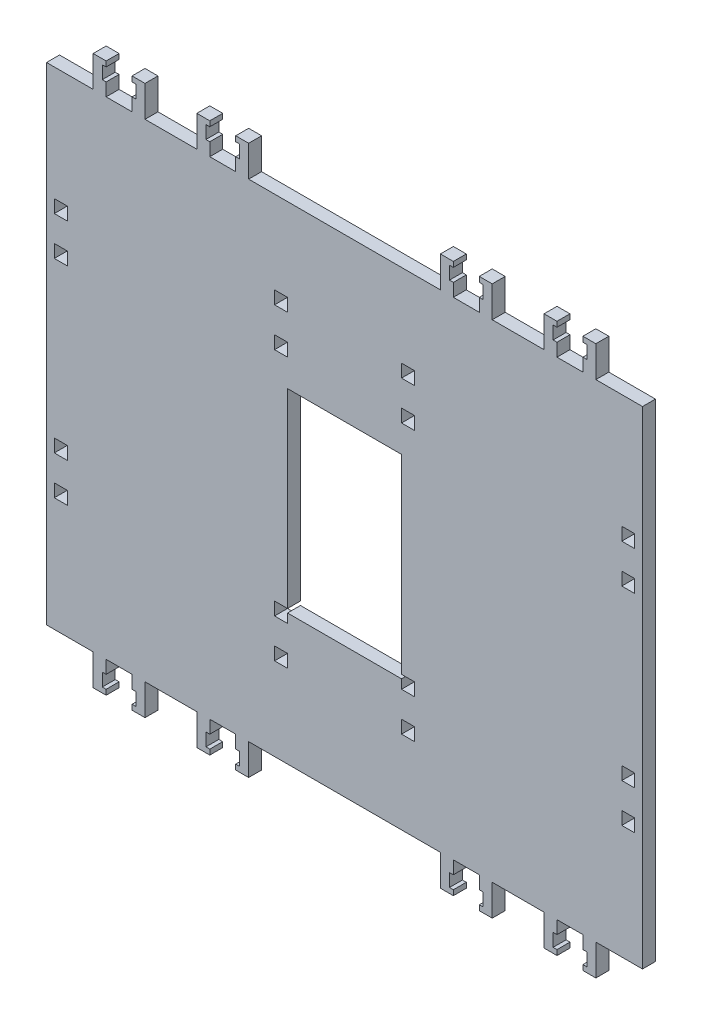
SolidWorks part; units mm, degrees
ref_plane "Plan de face" through (0, 0, 0) normal (0, 0, 1) x (1, 0, 0)
ref_plane "Plan de dessus" through (0, 0, 0) normal (0, 1, 0) x (1, 0, 0)
ref_plane "Plan de droite" through (0, 0, 0) normal (1, 0, 0) x (0, 0, -1)
sketch "Esquisse1" plane through (0, 0, 0) normal (0, 0, 1) x (1, 0, 0)
  line L0 (0, 0) -> (0, 94) construction
  line L1 (-21.3539, 94) -> (23.6911, 94) construction
  line L2 (-30, 188) -> (-45, 188)
  line L3 (-45, 188) -> (-45, 0) construction
  line L4 (-45, 0) -> (-30, 0)
  line L5 (-10, 0) -> (10, 0)
  line L6 (30, 0) -> (45, 0)
  line L7 (45, 0) -> (45, 188) construction
  line L8 (45, 188) -> (30, 188)
  line L9 (10, 188) -> (-10, 188)
  line L10 (-45, 188) -> (-45, 125.5) construction
  line L11 (-45, 125.5) -> (-89, 125.5)
  line L12 (-67, 125.5) -> (-67, 50.5) construction
  line L13 (-67, 50.5) -> (-45, 50.5)
  line L14 (-45, 50.5) -> (-45, 0) construction
  line L15 (-67, 50.5) -> (-89, 50.5)
  line L16 (-89, 50.5) -> (-89, 0) construction
  line L17 (-89, 0) -> (-104, 0)
  line L18 (-124, 0) -> (-144, 0)
  line L19 (-164, 0) -> (-179, 0)
  line L20 (-179, 0) -> (-179, 188) construction
  line L21 (-179, 188) -> (-164, 188)
  line L22 (-144, 188) -> (-124, 188)
  line L23 (-89, 188) -> (-89, 125.5) construction
  line L24 (-104, 188) -> (-89, 188)
  line L25 (-179, 0) -> (-179, 188) construction
  line L26 (-179, 0) -> (-174, 0) construction
  line L27 (-89, 125.5) -> (-89, 50.5)
  line L28 (-45, 50.5) -> (-45, 125.5)
  line L29 (-89, 188) -> (-45, 188)
  line L30 (-89, 0) -> (-45, 0)
  line L31 (45, 188) -> (48, 188)
  line L32 (48, 188) -> (48, 0)
  line L33 (48, 0) -> (45, 0)
  line L34 (-182, 0) -> (-179, 0)
  line L35 (-179, 188) -> (-182, 188)
  line L36 (-182, 188) -> (-182, 0)
  point P23 (-89, 33.0232)
  point P40 (0, 0)
  line B0 (20, 188) -> (20, 176.135) construction
  line B1 (20, 188) -> (15, 188)
  line B2 (15, 193) -> (10, 193) construction
  line B3 (10, 193) -> (10, 188)
  line B4 (15, 193) -> (15, 188)
  line B5 (20, 188) -> (25, 188)
  line B6 (25, 188) -> (25, 193)
  line B7 (25, 193) -> (30, 193) construction
  line B8 (30, 193) -> (30, 188)
  line B9 (10, 193) -> (10, 200)
  line B10 (10, 200) -> (15, 200)
  line B11 (15, 200) -> (15, 198)
  line B12 (15, 198) -> (13.5, 198)
  line B13 (13.5, 198) -> (13.5, 193)
  line B14 (13.5, 193) -> (15, 193)
  line B15 (25, 198) -> (26.5, 198)
  line B16 (30, 200) -> (25, 200)
  line B17 (25, 200) -> (25, 198)
  line B18 (26.5, 198) -> (26.5, 193)
  line B19 (30, 193) -> (30, 200)
  line B20 (30, 193) -> (30, 188)
  line B21 (25, 193) -> (26.5, 193)
  line B22 (-20, 188) -> (-20, 176.135) construction
  line B23 (-20, 188) -> (-25, 188)
  line B24 (-25, 193) -> (-30, 193) construction
  line B25 (-30, 193) -> (-30, 188)
  line B26 (-25, 193) -> (-25, 188)
  line B27 (-20, 188) -> (-15, 188)
  line B28 (-15, 188) -> (-15, 193)
  line B29 (-15, 193) -> (-10, 193) construction
  line B30 (-10, 193) -> (-10, 188)
  line B31 (-30, 193) -> (-30, 200)
  line B32 (-30, 200) -> (-25, 200)
  line B33 (-25, 200) -> (-25, 198)
  line B34 (-25, 198) -> (-26.5, 198)
  line B35 (-26.5, 198) -> (-26.5, 193)
  line B36 (-26.5, 193) -> (-25, 193)
  line B37 (-15, 198) -> (-13.5, 198)
  line B38 (-10, 200) -> (-15, 200)
  line B39 (-15, 200) -> (-15, 198)
  line B40 (-13.5, 198) -> (-13.5, 193)
  line B41 (-10, 193) -> (-10, 200)
  line B42 (-10, 193) -> (-10, 188)
  line B43 (-15, 193) -> (-13.5, 193)
  line B44 (20, 0) -> (20, 11.865) construction
  line B45 (20, 0) -> (15, 0)
  line B46 (15, -5) -> (10, -5) construction
  line B47 (10, -5) -> (10, 0)
  line B48 (15, -5) -> (15, 0)
  line B49 (20, 0) -> (25, 0)
  line B50 (25, 0) -> (25, -5)
  line B51 (25, -5) -> (30, -5) construction
  line B52 (30, -5) -> (30, 0)
  line B53 (10, -5) -> (10, -12)
  line B54 (10, -12) -> (15, -12)
  line B55 (15, -12) -> (15, -10)
  line B56 (15, -10) -> (13.5, -10)
  line B57 (13.5, -10) -> (13.5, -5)
  line B58 (13.5, -5) -> (15, -5)
  line B59 (25, -10) -> (26.5, -10)
  line B60 (30, -12) -> (25, -12)
  line B61 (25, -12) -> (25, -10)
  line B62 (26.5, -10) -> (26.5, -5)
  line B63 (30, -5) -> (30, -12)
  line B64 (30, -5) -> (30, 0)
  line B65 (25, -5) -> (26.5, -5)
  line B66 (-20, 0) -> (-20, 11.865) construction
  line B67 (-20, 0) -> (-25, 0)
  line B68 (-25, -5) -> (-30, -5) construction
  line B69 (-30, -5) -> (-30, 0)
  line B70 (-25, -5) -> (-25, 0)
  line B71 (-20, 0) -> (-15, 0)
  line B72 (-15, 0) -> (-15, -5)
  line B73 (-15, -5) -> (-10, -5) construction
  line B74 (-10, -5) -> (-10, 0)
  line B75 (-30, -5) -> (-30, -12)
  line B76 (-30, -12) -> (-25, -12)
  line B77 (-25, -12) -> (-25, -10)
  line B78 (-25, -10) -> (-26.5, -10)
  line B79 (-26.5, -10) -> (-26.5, -5)
  line B80 (-26.5, -5) -> (-25, -5)
  line B81 (-15, -10) -> (-13.5, -10)
  line B82 (-10, -12) -> (-15, -12)
  line B83 (-15, -12) -> (-15, -10)
  line B84 (-13.5, -10) -> (-13.5, -5)
  line B85 (-10, -5) -> (-10, -12)
  line B86 (-10, -5) -> (-10, 0)
  line B87 (-15, -5) -> (-13.5, -5)
  line B88 (-154, 188) -> (-154, 176.135) construction
  line B89 (-154, 188) -> (-149, 188)
  line B90 (-149, 193) -> (-144, 193) construction
  line B91 (-144, 193) -> (-144, 188)
  line B92 (-149, 193) -> (-149, 188)
  line B93 (-154, 188) -> (-159, 188)
  line B94 (-159, 188) -> (-159, 193)
  line B95 (-159, 193) -> (-164, 193) construction
  line B96 (-164, 193) -> (-164, 188)
  line B97 (-144, 193) -> (-144, 200)
  line B98 (-144, 200) -> (-149, 200)
  line B99 (-149, 200) -> (-149, 198)
  line B100 (-149, 198) -> (-147.5, 198)
  line B101 (-147.5, 198) -> (-147.5, 193)
  line B102 (-147.5, 193) -> (-149, 193)
  line B103 (-159, 198) -> (-160.5, 198)
  line B104 (-164, 200) -> (-159, 200)
  line B105 (-159, 200) -> (-159, 198)
  line B106 (-160.5, 198) -> (-160.5, 193)
  line B107 (-164, 193) -> (-164, 200)
  line B108 (-164, 193) -> (-164, 188)
  line B109 (-159, 193) -> (-160.5, 193)
  line B110 (-114, 0) -> (-114, 11.865) construction
  line B111 (-114, 0) -> (-109, 0)
  line B112 (-109, -5) -> (-104, -5) construction
  line B113 (-104, -5) -> (-104, 0)
  line B114 (-109, -5) -> (-109, 0)
  line B115 (-114, 0) -> (-119, 0)
  line B116 (-119, 0) -> (-119, -5)
  line B117 (-119, -5) -> (-124, -5) construction
  line B118 (-124, -5) -> (-124, 0)
  line B119 (-104, -5) -> (-104, -12)
  line B120 (-104, -12) -> (-109, -12)
  line B121 (-109, -12) -> (-109, -10)
  line B122 (-109, -10) -> (-107.5, -10)
  line B123 (-107.5, -10) -> (-107.5, -5)
  line B124 (-107.5, -5) -> (-109, -5)
  line B125 (-119, -10) -> (-120.5, -10)
  line B126 (-124, -12) -> (-119, -12)
  line B127 (-119, -12) -> (-119, -10)
  line B128 (-120.5, -10) -> (-120.5, -5)
  line B129 (-124, -5) -> (-124, -12)
  line B130 (-124, -5) -> (-124, 0)
  line B131 (-119, -5) -> (-120.5, -5)
  line B132 (-154, 0) -> (-154, 11.865) construction
  line B133 (-154, 0) -> (-149, 0)
  line B134 (-149, -5) -> (-144, -5) construction
  line B135 (-144, -5) -> (-144, 0)
  line B136 (-149, -5) -> (-149, 0)
  line B137 (-154, 0) -> (-159, 0)
  line B138 (-159, 0) -> (-159, -5)
  line B139 (-159, -5) -> (-164, -5) construction
  line B140 (-164, -5) -> (-164, 0)
  line B141 (-144, -5) -> (-144, -12)
  line B142 (-144, -12) -> (-149, -12)
  line B143 (-149, -12) -> (-149, -10)
  line B144 (-149, -10) -> (-147.5, -10)
  line B145 (-147.5, -10) -> (-147.5, -5)
  line B146 (-147.5, -5) -> (-149, -5)
  line B147 (-159, -10) -> (-160.5, -10)
  line B148 (-164, -12) -> (-159, -12)
  line B149 (-159, -12) -> (-159, -10)
  line B150 (-160.5, -10) -> (-160.5, -5)
  line B151 (-164, -5) -> (-164, -12)
  line B152 (-164, -5) -> (-164, 0)
  line B153 (-159, -5) -> (-160.5, -5)
  line B154 (-114, 188) -> (-114, 176.135) construction
  line B155 (-114, 188) -> (-109, 188)
  line B156 (-109, 193) -> (-104, 193) construction
  line B157 (-104, 193) -> (-104, 188)
  line B158 (-109, 193) -> (-109, 188)
  line B159 (-114, 188) -> (-119, 188)
  line B160 (-119, 188) -> (-119, 193)
  line B161 (-119, 193) -> (-124, 193) construction
  line B162 (-124, 193) -> (-124, 188)
  line B163 (-104, 193) -> (-104, 200)
  line B164 (-104, 200) -> (-109, 200)
  line B165 (-109, 200) -> (-109, 198)
  line B166 (-109, 198) -> (-107.5, 198)
  line B167 (-107.5, 198) -> (-107.5, 193)
  line B168 (-107.5, 193) -> (-109, 193)
  line B169 (-119, 198) -> (-120.5, 198)
  line B170 (-124, 200) -> (-119, 200)
  line B171 (-119, 200) -> (-119, 198)
  line B172 (-120.5, 198) -> (-120.5, 193)
  line B173 (-124, 193) -> (-124, 200)
  line B174 (-124, 193) -> (-124, 188)
  line B175 (-119, 193) -> (-120.5, 193)
  line B176 (42.5, 129) -> (42.5, 139) construction
  line B177 (40, 129) -> (40, 124)
  line B178 (40, 129) -> (45, 129)
  line B179 (45, 129) -> (45, 124)
  line B180 (40, 124) -> (45, 124)
  line B181 (40, 139) -> (40, 144)
  line B182 (40, 139) -> (45, 139)
  line B183 (45, 139) -> (45, 144)
  line B184 (40, 144) -> (45, 144)
  line B185 (42.5, 134) -> (35.5276, 134) construction
  circle B186 centre (42.5, 134) radius 2 construction
  line B187 (42.5, 59) -> (42.5, 49) construction
  line B188 (40, 59) -> (40, 64)
  line B189 (40, 59) -> (45, 59)
  line B190 (45, 59) -> (45, 64)
  line B191 (40, 64) -> (45, 64)
  line B192 (40, 49) -> (40, 44)
  line B193 (40, 49) -> (45, 49)
  line B194 (45, 49) -> (45, 44)
  line B195 (40, 44) -> (45, 44)
  line B196 (42.5, 54) -> (35.5276, 54) construction
  circle B197 centre (42.5, 54) radius 2 construction
  line B198 (-176.5, 129) -> (-176.5, 139) construction
  line B199 (-174, 129) -> (-174, 124)
  line B200 (-174, 129) -> (-179, 129)
  line B201 (-179, 129) -> (-179, 124)
  line B202 (-174, 124) -> (-179, 124)
  line B203 (-174, 139) -> (-174, 144)
  line B204 (-174, 139) -> (-179, 139)
  line B205 (-179, 139) -> (-179, 144)
  line B206 (-174, 144) -> (-179, 144)
  line B207 (-176.5, 134) -> (-169.5276, 134) construction
  circle B208 centre (-176.5, 134) radius 2 construction
  line B209 (-176.5, 59) -> (-176.5, 49) construction
  line B210 (-174, 59) -> (-174, 64)
  line B211 (-174, 59) -> (-179, 59)
  line B212 (-179, 59) -> (-179, 64)
  line B213 (-174, 64) -> (-179, 64)
  line B214 (-174, 49) -> (-174, 44)
  line B215 (-174, 49) -> (-179, 49)
  line B216 (-179, 49) -> (-179, 44)
  line B217 (-174, 44) -> (-179, 44)
  line B218 (-176.5, 54) -> (-169.5276, 54) construction
  circle B219 centre (-176.5, 54) radius 2 construction
  line B220 (-91.5, 141) -> (-91.5, 151) construction
  line B221 (-89, 141) -> (-89, 136)
  line B222 (-89, 141) -> (-94, 141)
  line B223 (-94, 141) -> (-94, 136)
  line B224 (-89, 136) -> (-94, 136)
  line B225 (-89, 151) -> (-89, 156)
  line B226 (-89, 151) -> (-94, 151)
  line B227 (-94, 151) -> (-94, 156)
  line B228 (-89, 156) -> (-94, 156)
  line B229 (-91.5, 146) -> (-84.5276, 146) construction
  circle B230 centre (-91.5, 146) radius 2 construction
  line B231 (-42.5, 141) -> (-42.5, 151) construction
  line B232 (-45, 141) -> (-45, 136)
  line B233 (-45, 141) -> (-40, 141)
  line B234 (-40, 141) -> (-40, 136)
  line B235 (-45, 136) -> (-40, 136)
  line B236 (-45, 151) -> (-45, 156)
  line B237 (-45, 151) -> (-40, 151)
  line B238 (-40, 151) -> (-40, 156)
  line B239 (-45, 156) -> (-40, 156)
  line B240 (-42.5, 146) -> (-49.4724, 146) construction
  circle B241 centre (-42.5, 146) radius 2 construction
  line B242 (-91.5, 37) -> (-91.5, 47) construction
  line B243 (-89, 37) -> (-89, 32)
  line B244 (-89, 37) -> (-94, 37)
  line B245 (-94, 37) -> (-94, 32)
  line B246 (-89, 32) -> (-94, 32)
  line B247 (-89, 47) -> (-89, 52)
  line B248 (-89, 47) -> (-94, 47)
  line B249 (-94, 47) -> (-94, 52)
  line B250 (-89, 52) -> (-94, 52)
  line B251 (-91.5, 42) -> (-84.5276, 42) construction
  circle B252 centre (-91.5, 42) radius 2 construction
  line B253 (-42.5, 37) -> (-42.5, 47) construction
  line B254 (-45, 37) -> (-45, 32)
  line B255 (-45, 37) -> (-40, 37)
  line B256 (-40, 37) -> (-40, 32)
  line B257 (-45, 32) -> (-40, 32)
  line B258 (-45, 47) -> (-45, 52)
  line B259 (-45, 47) -> (-40, 47)
  line B260 (-40, 47) -> (-40, 52)
  line B261 (-45, 52) -> (-40, 52)
  line B262 (-42.5, 42) -> (-49.4724, 42) construction
  circle B263 centre (-42.5, 42) radius 2 construction
  dimension "D2" = 15
  dimension "D3" = 15
  dimension "D4" = 188
  dimension "D5" = 75
  dimension "D1" = 40
  dimension "D6" = 188
  dimension "D7" = 224
  dimension "D8" = 80
  dimension "D9" = 3
  dimension "D10" = 42
  dimension "D11" = 32
sketch_block_instance "Insert plots ep 5mm avec ergots-8"
sketch_block "Insert plots ep 5mm avec ergots" parameters "D1"=10, "D2"=5, "D3"=5, "D4"=5, "D5"=2, "D6"=1.5, "D7"=2, "D8"=2, "D9"=2.0716, "D10"=2
sketch_block_instance "Insert plots ep 5mm avec ergots-9"
sketch_block_instance "Insert plots ep 5mm avec ergots-10"
sketch_block_instance "Insert plots ep 5mm avec ergots-11"
sketch_block_instance "Insert plots ep 5mm avec ergots-12"
sketch_block_instance "Insert plots ep 5mm avec ergots-13"
sketch_block_instance "Insert plots ep 5mm avec ergots-14"
sketch_block_instance "Insert plots ep 5mm avec ergots-15"
sketch_block_instance "Trou M4 plots 5mm-1"
sketch_block "Trou M4 plots 5mm" parameters "D2"=4, "D5"=4, "D1"=5, "D3"=5, "D4"=10
sketch_block_instance "Trou M4 plots 5mm-3"
sketch_block_instance "Trou M4 plots 5mm-4"
sketch_block_instance "Trou M4 plots 5mm-5"
sketch_block_instance "Trou M4 plots 5mm-6"
sketch_block_instance "Trou M4 plots 5mm-7"
sketch_block_instance "Trou M4 plots 5mm-8"
sketch_block_instance "Trou M4 plots 5mm-9" parameters "D1"=0, "D2"=11.4238, "D3"=90.6659, "D4"=90.4393, "D5"=188, "D6"=84.7334, "D7"=22, "D8"=188, "D9"=7.14, "D10"=1.5, "D11"=90, "D12"=90
extrude "Boss.-Extru.1" add sketch "Esquisse1" along normal blind 5 contours L2 L3 L4 L5 L6 L7 L8 L9 region at (-26.872, 190.5, 0)
